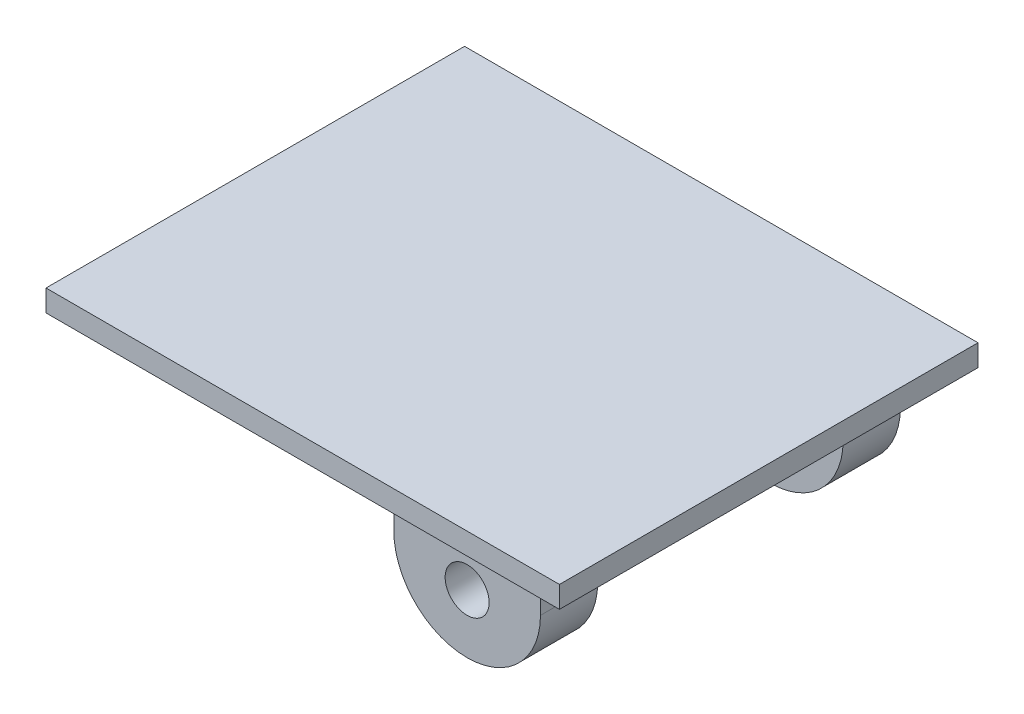
SolidWorks part; units mm, degrees
ref_plane "Front Plane" through (0, 0, 0) normal (0, 0, 1) x (1, 0, 0)
ref_plane "Top Plane" through (0, 0, 0) normal (0, 1, 0) x (1, 0, 0)
ref_plane "Right Plane" through (0, 0, 0) normal (1, 0, 0) x (0, 0, -1)
sketch "Sketch2" plane through (0, 0, 0) normal (1, 0, 0) x (0, 0, -1)
  line L0 (-2685.2072, -1340.267) -> (-2685.2072, -1192.9703)
  line L1 (-2685.2072, -1192.9703) -> (168.1056, -1192.9703)
  line L2 (168.1056, -1192.9703) -> (168.1056, -1340.267)
  line L3 (168.1056, -1340.267) -> (-2685.2072, -1340.267)
  point P4 (0, 0)
  point P9 (0, 0)
  point P10 (-2666.6797, -1192.9703)
extrude "Boss-Extrude1" add sketch "Sketch2" along normal blind 2000 and the other way blind 1500
ref_plane "Plane1" through (0, 0, 31.8944) normal (0, 0, -1) x (-1, 0, 0)
sketch "Sketch3" plane through (0, 0, 31.8944) normal (0, 0, -1) x (-1, 0, 0)
  line L0 (-1670.7603, -1340.267) -> (-1670.7603, -1640.267)
  line L1 (-670.7603, -1340.267) -> (-670.7603, -1640.267)
  line L2 (1500, -1340.267) -> (-2000, -1340.267) construction
  line L3 (-1670.7603, -1340.267) -> (-670.7603, -1340.267)
  arc A0 (-1670.7603, -1640.267) -> (-670.7603, -1640.267) centre (-1170.7603, -1640.267) ccw
  circle A1 centre (-1170.7603, -1740.267) radius 150
  point P2 (-1170.7603, -1767.4843)
  point P10 (-1024.4968, -2027.6037)
  point P11 (0, 0)
  dimension "D1" = 300
  dimension "D2" = 1000
  dimension "D3" = 300
  dimension "D4" = 300
  dimension "D5" = 400
extrude "Boss-Extrude2" add sketch "Sketch3" against normal blind 390 contours L0 A0 L1 L3 A1 region at (1170.7603, -1353.0733, 31.8944)
ref_plane "Plane2" through (0, 0, 2485.2072) normal (0, 0, 1) x (1, 0, 0)
sketch "Sketch5" plane through (0, 0, 2485.2072) normal (0, 0, 1) x (1, 0, 0)
  line L0 (670.7603, -1340.267) -> (1670.7603, -1340.267)
  line L5 (1670.7603, -1340.267) -> (1670.7603, -1640.267)
  line L6 (670.7603, -1640.267) -> (670.7603, -1340.267)
  arc A2 (670.7603, -1640.267) -> (1670.7603, -1640.267) centre (1170.7603, -1640.267) ccw
  circle A5 centre (1170.7603, -1740.267) radius 150
extrude "Boss-Extrude3" add sketch "Sketch5" against normal blind 390
